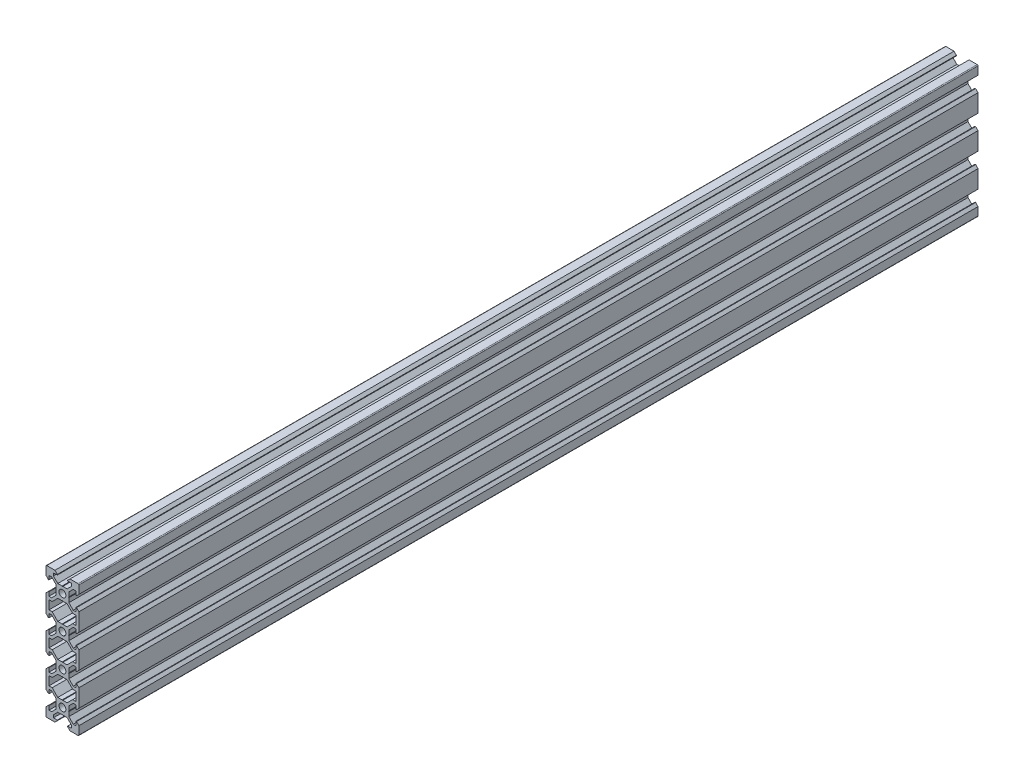
SolidWorks part; units mm, degrees
ref_plane "Plan de face" through (0, 0, 0) normal (0, 0, 1) x (1, 0, 0)
ref_plane "Plan de dessus" through (0, 0, 0) normal (0, 1, 0) x (1, 0, 0)
ref_plane "Plan de droite" through (0, 0, 0) normal (1, 0, 0) x (0, 0, -1)
ref_axis "Axe" through (0, 0, -13.782) along (0, 0, 1)
sketch "Esquisse1" plane through (0, 0, 0) normal (0, 0, 1) x (1, 0, 0)
  line L0 (0, 27.6392) -> (0, -27.6392) construction
  line L1 (-33.6074, 0) -> (33.6074, 0) construction
  line L2 (0, 0) -> (-22.2114, 22.2114) construction
  line L3 (-9.5, 10) -> (-4.58, 10)
  line L4 (-4.58, 10) -> (-3.125, 8.545)
  line L5 (-3.125, 8.545) -> (-3.125, 8.2)
  line L6 (-3.125, 8.2) -> (-5.5, 8.2)
  line L7 (-2.8393, 3.9) -> (-5.5, 6.5607)
  line L8 (-2.8393, 3.9) -> (-0.21, 3.9)
  line L9 (-5.5, 6.5607) -> (-5.5, 8.2)
  line L10 (0, 3.69) -> (0, 2.1)
  line L11 (-3.9, 2.8393) -> (-6.5607, 5.5)
  line L12 (-8.545, 3.125) -> (-8.2, 3.125)
  line L13 (-8.2, 3.125) -> (-8.2, 5.5)
  line L14 (-6.5607, 5.5) -> (-8.2, 5.5)
  line L15 (-10, 4.58) -> (-8.545, 3.125)
  line L16 (-10, 9.5) -> (-10, 4.58)
  line L17 (-0.21, 3.9) -> (0, 3.69)
  line L18 (-3.9, 2.8393) -> (-3.9, 0.21)
  line L19 (-6.2393, -12.7) -> (-8.2, -12.7)
  line L20 (-3.9, 0.21) -> (-3.69, 0)
  line L21 (-0.21, -3.9) -> (0, -3.69)
  line L22 (0, -3.69) -> (0, -2.1)
  line L23 (-6.5607, -5.5) -> (-8.2, -5.5)
  line L24 (-2.8393, -3.9) -> (-0.21, -3.9)
  line L25 (-8.545, -3.125) -> (-8.2, -3.125)
  line L26 (-10, -4.58) -> (-8.545, -3.125)
  line L27 (-8.2, -3.125) -> (-8.2, -5.5)
  line L28 (-2.8393, -3.9) -> (-6.2393, -7.3)
  line L29 (-3.9, -2.8393) -> (-6.5607, -5.5)
  line L30 (-3.9, -2.8393) -> (-3.9, -0.21)
  line L31 (-3.9, -0.21) -> (-3.69, 0)
  line L32 (-6.2393, -7.3) -> (-8.2, -7.3)
  line L33 (-8.2, -7.3) -> (-8.2, -12.7)
  line L34 (-8.2, -10) -> (-10, -10) construction
  line L35 (-10, -15.42) -> (-10, -4.58)
  line L36 (-3.9, -19.79) -> (-3.69, -20)
  line L37 (-3.9, -17.1607) -> (-3.9, -19.79)
  line L38 (-3.9, -17.1607) -> (-6.5607, -14.5)
  line L39 (-2.8393, -16.1) -> (-6.2393, -12.7)
  line L40 (-8.2, -16.875) -> (-8.2, -14.5)
  line L41 (-10, -15.42) -> (-8.545, -16.875)
  line L42 (-8.545, -16.875) -> (-8.2, -16.875)
  line L43 (-2.8393, -16.1) -> (-0.21, -16.1)
  line L44 (-6.5607, -14.5) -> (-8.2, -14.5)
  line L45 (0, -16.31) -> (0, -17.9)
  line L46 (-0.21, -16.1) -> (0, -16.31)
  line L47 (-8.2, -30) -> (-10, -30) construction
  line L48 (-3.69, -20) -> (0, -20) construction
  line L49 (-0.21, -23.9) -> (0, -23.69)
  line L50 (0, -23.69) -> (0, -22.1)
  line L51 (-6.5607, -25.5) -> (-8.2, -25.5)
  line L52 (-2.8393, -23.9) -> (-0.21, -23.9)
  line L53 (-8.545, -23.125) -> (-8.2, -23.125)
  line L54 (-10, -24.58) -> (-8.545, -23.125)
  line L55 (-8.2, -23.125) -> (-8.2, -25.5)
  line L56 (-2.8393, -23.9) -> (-6.2393, -27.3)
  line L57 (-3.9, -22.8393) -> (-6.5607, -25.5)
  line L58 (-3.9, -22.8393) -> (-3.9, -20.21)
  line L59 (-3.9, -20.21) -> (-3.69, -20)
  line L60 (-10, -24.58) -> (-10, -35.42)
  line L61 (-8.2, -32.7) -> (-8.2, -27.3)
  line L62 (-3.69, -40) -> (0, -40) construction
  line L63 (-8.2, -50) -> (-10, -50) construction
  line L64 (0, -60) -> (-22.2114, -82.2114) construction
  line L65 (-33.6074, -60) -> (33.6074, -60) construction
  line L66 (0, -87.6392) -> (0, -32.3608) construction
  line L67 (-6.2393, -32.7) -> (-8.2, -32.7)
  line L68 (-3.9, -39.79) -> (-3.69, -40)
  line L69 (-3.9, -37.1607) -> (-3.9, -39.79)
  line L70 (-3.9, -37.1607) -> (-6.5607, -34.5)
  line L71 (-2.8393, -36.1) -> (-6.2393, -32.7)
  line L72 (-8.2, -36.875) -> (-8.2, -34.5)
  line L73 (-10, -35.42) -> (-8.545, -36.875)
  line L74 (-8.545, -36.875) -> (-8.2, -36.875)
  line L75 (-6.2393, -27.3) -> (-8.2, -27.3)
  line L76 (-2.8393, -36.1) -> (-0.21, -36.1)
  line L77 (-6.5607, -34.5) -> (-8.2, -34.5)
  line L78 (0, -36.31) -> (0, -37.9)
  line L79 (-0.21, -36.1) -> (0, -36.31)
  line L80 (-0.21, -43.9) -> (0, -43.69)
  line L81 (0, -43.69) -> (0, -42.1)
  line L82 (-6.5607, -45.5) -> (-8.2, -45.5)
  line L83 (-2.8393, -43.9) -> (-0.21, -43.9)
  line L84 (-8.545, -43.125) -> (-8.2, -43.125)
  line L85 (-10, -44.58) -> (-8.545, -43.125)
  line L86 (-8.2, -43.125) -> (-8.2, -45.5)
  line L87 (-2.8393, -43.9) -> (-6.2393, -47.3)
  line L88 (-3.9, -42.8393) -> (-6.5607, -45.5)
  line L89 (-3.9, -42.8393) -> (-3.9, -40.21)
  line L90 (-3.9, -40.21) -> (-3.69, -40)
  line L91 (-10, -44.58) -> (-10, -55.42)
  line L92 (-8.2, -52.7) -> (-8.2, -47.3)
  line L93 (-6.2393, -52.7) -> (-8.2, -52.7)
  line L94 (-3.9, -59.79) -> (-3.69, -60)
  line L95 (-3.9, -57.1607) -> (-3.9, -59.79)
  line L96 (-3.9, -57.1607) -> (-6.5607, -54.5)
  line L97 (-2.8393, -56.1) -> (-6.2393, -52.7)
  line L98 (-8.2, -56.875) -> (-8.2, -54.5)
  line L99 (-10, -55.42) -> (-8.545, -56.875)
  line L100 (-8.545, -56.875) -> (-8.2, -56.875)
  line L101 (-2.8393, -56.1) -> (-0.21, -56.1)
  line L102 (-6.5607, -54.5) -> (-8.2, -54.5)
  line L103 (0, -56.31) -> (0, -57.9)
  line L104 (-0.21, -56.1) -> (0, -56.31)
  line L105 (-3.9, -60.21) -> (-3.69, -60)
  line L106 (-6.2393, -47.3) -> (-8.2, -47.3)
  line L107 (-3.9, -62.8393) -> (-3.9, -60.21)
  line L108 (-0.21, -63.9) -> (0, -63.69)
  line L109 (-10, -69.5) -> (-10, -64.58)
  line L110 (-10, -64.58) -> (-8.545, -63.125)
  line L111 (-6.5607, -65.5) -> (-8.2, -65.5)
  line L112 (-8.2, -63.125) -> (-8.2, -65.5)
  line L113 (-8.545, -63.125) -> (-8.2, -63.125)
  line L114 (-3.9, -62.8393) -> (-6.5607, -65.5)
  line L115 (0, -63.69) -> (0, -62.1)
  line L116 (-5.5, -66.5607) -> (-5.5, -68.2)
  line L117 (-2.8393, -63.9) -> (-0.21, -63.9)
  line L118 (-2.8393, -63.9) -> (-5.5, -66.5607)
  line L119 (-3.125, -68.2) -> (-5.5, -68.2)
  line L120 (-3.125, -68.545) -> (-3.125, -68.2)
  line L121 (-4.58, -70) -> (-3.125, -68.545)
  line L122 (-9.5, -70) -> (-4.58, -70)
  arc A0 (0, -2.1) -> (0, 2.1) centre (0, 0) cw
  arc A1 (-9.5, 10) -> (-10, 9.5) centre (-9.5, 9.5) ccw
  arc A2 (0, -42.1) -> (0, -37.9) centre (0, -40) cw
  arc A3 (-9.5, -70) -> (-10, -69.5) centre (-9.5, -69.5) cw
  arc A4 (0, -17.9) -> (0, -22.1) centre (0, -20) ccw
  arc A5 (0, -57.9) -> (0, -62.1) centre (0, -60) ccw
  point P4 (0, 0)
  point P7 (0, 0)
  point P30 (-10, 10)
  point P60 (0, -20)
  point P146 (-10, -70)
  dimension "D5" = 11
  dimension "D2" = 2.1
  dimension "D3" = 6.25
  dimension "D10" = 0.5
  dimension "D4" = 9.16
  dimension "D6" = 1.5
  dimension "D7" = 1.8
  dimension "D8" = 4.3
  dimension "D9" = 20
  dimension "D11" = 0.42
  dimension "D12" = 10
  dimension "D13" = 1.8
extrude "Boss.-Extru.1" add sketch "Esquisse1" along normal blind 546.8
sketch "Esquisse3" plane through (0, 0, 546.8) normal (0, 0, 1) x (1, 0, 0)
  line L0 (0, 0) -> (-9.8536, 9.8536) construction
  line L1 (-8.2, 8.2) -> (-8.2, 6.57)
  line L2 (-8.2, 6.57) -> (-7.54, 6.57)
  line L3 (-7.54, 6.57) -> (-6.57, 7.54)
  line L4 (-8.2, 3.125) -> (-8.2, 5.5) construction
  line L5 (-6.57, 8.2) -> (-6.57, 7.54)
  line L6 (-8.2, 8.2) -> (-6.57, 8.2)
  line L7 (-5.5, 6.5607) -> (-5.5, 8.2) construction
  line L8 (-10, -30) -> (6.918, -30) construction
  line L9 (-10, -24.58) -> (-10, -35.42) construction
  line L10 (-8.2, -68.2) -> (-6.57, -68.2)
  line L11 (-6.57, -68.2) -> (-6.57, -67.54)
  line L12 (-7.54, -66.57) -> (-6.57, -67.54)
  line L13 (-8.2, -66.57) -> (-7.54, -66.57)
  line L14 (-8.2, -68.2) -> (-8.2, -66.57)
  arc A0 (-9.5, 10) -> (-10, 9.5) centre (-9.5, 9.5) ccw construction
  point P13 (-7.055, 7.055)
  point P14 (-6.57, 7.87)
  point P26 (-7.055, -67.055)
  dimension "D1" = 1.07
extrude "Enlèv. mat.-Extru.1" [suppressed] cut sketch "Esquisse3" against normal through all
mirror "Symétrie1" about plane through (0, 3.69, 546.8) normal (-1, 0, 0) of "Enlèv. mat.-Extru.1", "Boss.-Extru.1"
